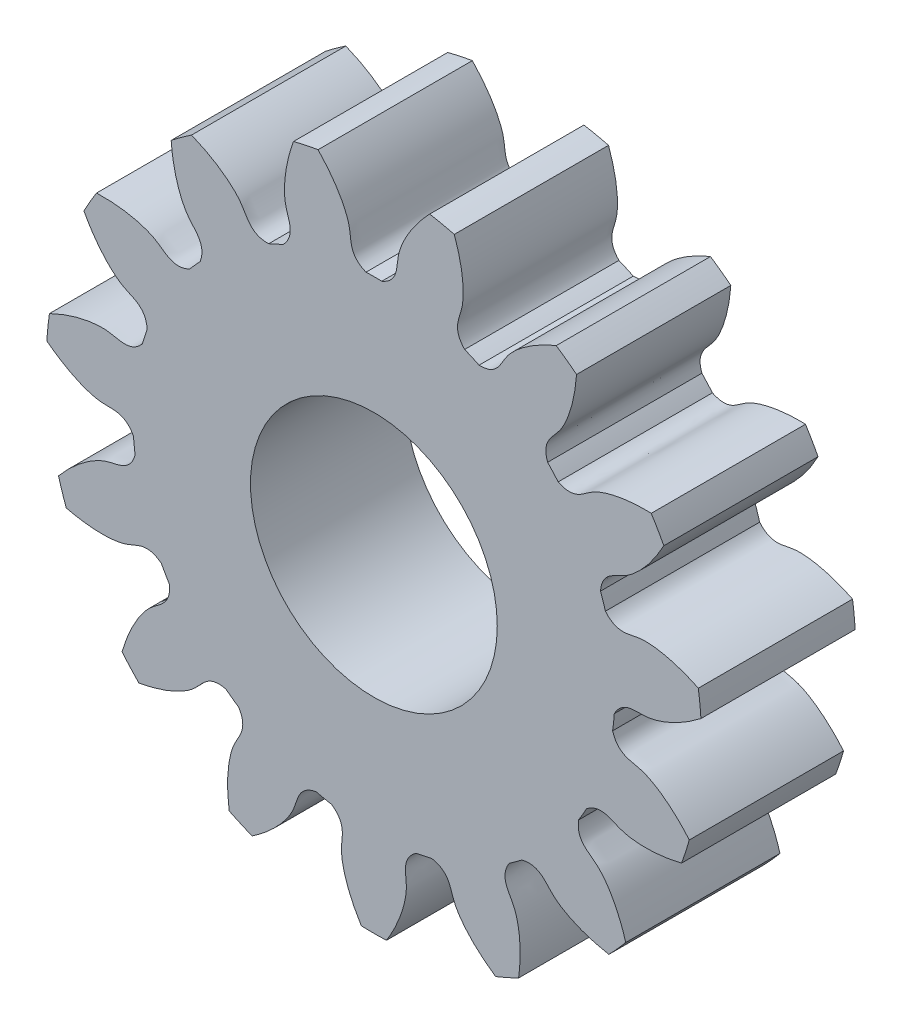
SolidWorks part; units mm, degrees
ref_plane "前视基准面" through (0, 0, 0) normal (0, 0, 1) x (1, 0, 0)
ref_plane "上视基准面" through (0, 0, 0) normal (0, 1, 0) x (1, 0, 0)
ref_plane "右视基准面" through (0, 0, 0) normal (1, 0, 0) x (0, 0, -1)
sketch "草图1" plane through (0, 0, 0) normal (0, 0, 1) x (1, 0, 0)
  circle A0 centre (0, 0) radius 4.25
extrude "凸台-拉伸1" add sketch "草图1" along normal blind 2
ref_axis "基准轴1" through (0, 0, 2) along (0, 0, -1)
sketch "草图2" plane through (0, 0, 0) normal (0, 0, 1) x (1, 0, 0)
  line L0 (0, 0) -> (0, 4.25) construction
  circle A0 centre (0, 0) radius 4.25 construction
  arc A1 (0.1021, 3.1233) -> (-0.1021, 3.1233) centre (0, 0) ccw
  arc A2 (1.6234, 4.818) -> (-1.6234, 4.818) centre (0, 0) ccw
  spline S0 degree 3 poles (0.1021, 3.1233) (0.3286, 3.2172) (0.2861, 3.3932) (0.3256, 3.5543) (0.3287, 3.5658) (0.3324, 3.5787) (0.3368, 3.5928) (0.3419, 3.6082) (0.3478, 3.6248) (0.3545, 3.6426) (0.3621, 3.6616) (0.3706, 3.6817) (0.3801, 3.703) (0.3906, 3.7253) (0.4022, 3.7486) (0.4149, 3.773) (0.4288, 3.7984) (0.4438, 3.8247) (0.4601, 3.8519) (0.4777, 3.8799) (0.4967, 3.9088) (0.517, 3.9385) (0.5387, 3.9689) (0.5618, 4) (0.5865, 4.0317) (0.6126, 4.064) (0.6403, 4.0969) (0.6696, 4.1303) (0.7005, 4.1641) (0.733, 4.1983) (0.7673, 4.2329) (0.8032, 4.2678) (0.8408, 4.3029) (0.8801, 4.3381) (0.9213, 4.3735) (0.9642, 4.409) (1.0089, 4.4445) (1.0555, 4.4799) (1.1039, 4.5153) (1.1541, 4.5504) (1.2062, 4.5854) (1.2602, 4.62) (1.316, 4.6543) (1.3738, 4.6882) (1.4334, 4.7216) (1.5163, 4.7659) (1.5801, 4.7975) (1.6234, 4.818) knots 0 0 0 0 0.202473 0.206979 0.212085 0.217793 0.224101 0.23101 0.23852 0.24663 0.255341 0.264653 0.274566 0.285079 0.296194 0.307909 0.320225 0.333141 0.346659 0.360777 0.375496 0.390816 0.406736 0.423257 0.440379 0.458102 0.476426 0.49535 0.514875 0.535001 0.555728 0.577055 0.598984 0.621513 0.644642 0.668373 0.692704 0.717636 0.743169 0.769303 0.796037 0.823373 0.851309 0.879845 0.908983 0.938721 1 1 1 1
  spline S1 degree 3 poles (-0.1021, 3.1233) (-0.3286, 3.2172) (-0.2861, 3.3932) (-0.3256, 3.5543) (-0.3287, 3.5658) (-0.3324, 3.5787) (-0.3368, 3.5928) (-0.3419, 3.6082) (-0.3478, 3.6248) (-0.3545, 3.6426) (-0.3621, 3.6616) (-0.3706, 3.6817) (-0.3801, 3.703) (-0.3906, 3.7253) (-0.4022, 3.7486) (-0.4149, 3.773) (-0.4288, 3.7984) (-0.4438, 3.8247) (-0.4601, 3.8519) (-0.4777, 3.8799) (-0.4967, 3.9088) (-0.517, 3.9385) (-0.5387, 3.9689) (-0.5618, 4) (-0.5865, 4.0317) (-0.6126, 4.064) (-0.6403, 4.0969) (-0.6696, 4.1303) (-0.7005, 4.1641) (-0.733, 4.1983) (-0.7673, 4.2329) (-0.8032, 4.2678) (-0.8408, 4.3029) (-0.8801, 4.3381) (-0.9213, 4.3735) (-0.9642, 4.409) (-1.0089, 4.4445) (-1.0555, 4.4799) (-1.1039, 4.5153) (-1.1541, 4.5504) (-1.2062, 4.5854) (-1.2602, 4.62) (-1.316, 4.6543) (-1.3738, 4.6882) (-1.4334, 4.7216) (-1.5163, 4.7659) (-1.5801, 4.7975) (-1.6234, 4.818) knots 0 0 0 0 0.202473 0.206979 0.212085 0.217793 0.224101 0.23101 0.23852 0.24663 0.255341 0.264653 0.274566 0.285079 0.296194 0.307909 0.320225 0.333141 0.346659 0.360777 0.375496 0.390816 0.406736 0.423257 0.440379 0.458102 0.476426 0.49535 0.514875 0.535001 0.555728 0.577055 0.598984 0.621513 0.644642 0.668373 0.692704 0.717636 0.743169 0.769303 0.796037 0.823373 0.851309 0.879845 0.908983 0.938721 1 1 1 1
extrude "切除-拉伸1" cut sketch "草图2" along normal through all
pattern_circular "阵列(圆周)1" count 15 every 24 about axis through (0, 0, 2) along (0, 0, -1) of "切除-拉伸1"
sketch "草图3" plane through (0, 0, 0) normal (0, 0, 1) x (1, 0, 0)
  circle A0 centre (0, 0) radius 3.75 construction
  dimension "Dn" = 7.5
sketch "草图4" plane through (0, 0, 2) normal (0, 0, 1) x (1, 0, 0)
  circle A0 centre (0, 0) radius 1.6
  dimension "D1" = 3.2
extrude "切除-拉伸2" cut sketch "草图4" against normal up to next
